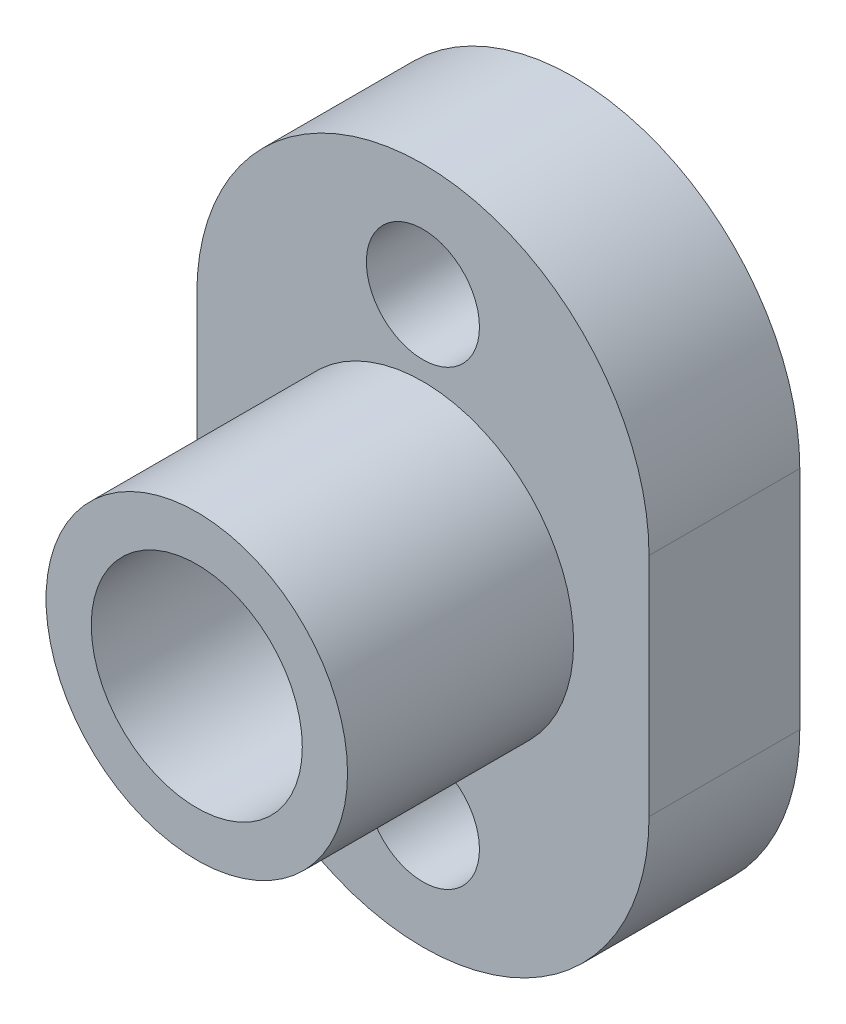
SolidWorks part; units mm, degrees
ref_plane "Płaszczyzna przednia" through (0, 0, 0) normal (0, 0, 1) x (1, 0, 0)
ref_plane "Płaszczyzna górna" through (0, 0, 0) normal (0, 1, 0) x (1, 0, 0)
ref_plane "Płaszczyzna prawa" through (0, 0, 0) normal (1, 0, 0) x (0, 0, -1)
sketch "Sketch3" plane through (0, 0, 0) normal (0, 0, 1) x (1, 0, 0)
  line L0 (0, 6.6675) -> (0, -5.7261) construction
  line L1 (-6.131, 0) -> (5.7784, 0) construction
  line L2 (-6, 3) -> (-6, -3)
  line L3 (6, 3) -> (6, -3)
  circle A0 centre (0, 0) radius 3
  circle A1 centre (0, -3) radius 6
  circle A2 centre (0, 3) radius 6
  circle A3 centre (0, -6) radius 1.5
  circle A4 centre (0, 0) radius 2.8
  circle A5 centre (0, 0) radius 4
  circle A6 centre (0, 6) radius 1.5
  point P14 (6, 0)
  point P15 (-6, 0)
  dimension "D1" = 6
  dimension "D2" = 12
  dimension "D3" = 3
  dimension "D5" = 5.6
  dimension "D6" = 8
  dimension "D4" = 6
extrude "Boss-Extrude1" add sketch "Sketch3" along normal blind 4 contours A5 A1 A2 A6 | A1 A2 L2 | L3 A2 A1 | A1 A5 | A1 A5 A2 A0 | A5 A1 A2 | A5 A2 A1 A3 | A0 A4 | A2 A5 | A5 A2 A1 | A2 A5 A1 A0 region at (-5.7619, 0, 0) region at (0, 8.85, 0) region at (-5.6507, -1.4859, 0) region at (5.7619, 0, 0) region at (-4.3323, 0, 0) region at (4.3323, 0, 0) region at (0, 3.1671, 0) region at (-1.8483, 2.6324, 0) region at (0, -3.1671, 0) region at (3.8171, 0.9263, 0) region at (2.0613, 2.0613, 0)
extrude "Boss-Extrude2" add sketch "Sketch3<3>" along normal blind 10 contours A1 A5 | A1 A5 A2 A0 | A0 A4 | A2 A5 A1 A0 | A2 A5 region at (0, 3.1671, 0) region at (-1.8483, 2.6324, 0) region at (0, -3.1671, 0) region at (3.8171, 0.9263, 0) region at (2.0613, 2.0613, 0)
sketch "Sketch3<3>" plane through (0, 0, 0) normal (0, 0, 1) x (1, 0, 0) same geometry as "Sketch3"
